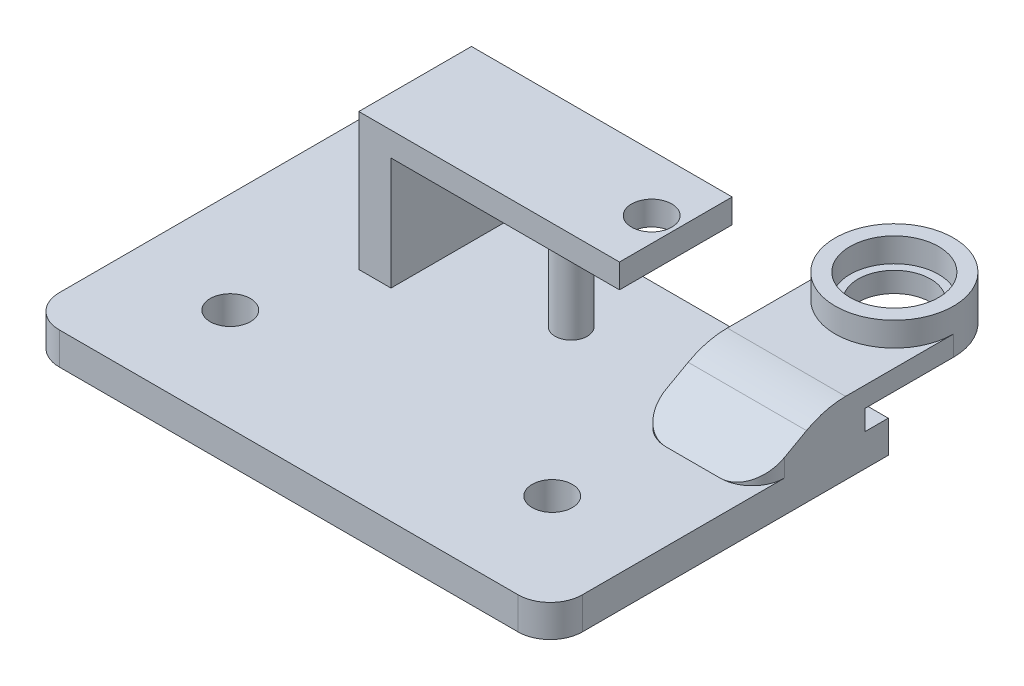
SolidWorks part; units mm, degrees
ref_plane "Front Plane" through (0, 0, 0) normal (0, 0, 1) x (1, 0, 0)
ref_plane "Top Plane" through (0, 0, 0) normal (0, 1, 0) x (1, 0, 0)
ref_plane "Right Plane" through (0, 0, 0) normal (1, 0, 0) x (0, 0, -1)
sketch "Sketch1" plane through (0, 0, 0) normal (0, 1, 0) x (1, 0, 0)
  line L1 (4, 0) -> (61, 0)
  line L2 (0, 4) -> (0, 42)
  line L3 (0, 42) -> (65, 42)
  line L4 (65, 4) -> (65, 42)
  arc A0 (65, 4) -> (61, 0) centre (61, 4) cw
  arc A1 (0, 4) -> (4, 0) centre (4, 4) ccw
  circle A2 centre (12.5, 12.75) radius 2.5
  circle A3 centre (52.5, 12.75) radius 2.5
  point P7 (65, 0)
  point P10 (0, 0)
  dimension "D3" = 4
  dimension "D8" = 5
  dimension "D9" = 5
  dimension "D1" = 42
  dimension "D2" = 65
  dimension "D4" = 12.75
  dimension "D5" = 40
  dimension "D6" = 12.75
  dimension "D7" = 12.5
extrude "Boss-Extrude1" add sketch "Sketch1" along normal blind 4
sketch "Sketch2" plane through (0, 4, 0) normal (0, 1, 0) x (1, 0, 0)
  line L0 (0, 42) -> (0, 4) construction
  line L1 (65, 42) -> (0, 42)
  line L2 (65, 42) -> (65, 38)
  line L3 (65, 38) -> (0, 38)
  line L4 (0, 42) -> (0, 38)
  circle A0 centre (61, 4) radius 2
  circle A1 centre (4, 4) radius 2
  dimension "D1" = 4
  dimension "D2" = 4
  dimension "D3" = 4
extrude "Boss-Extrude2" add sketch "Sketch2" along normal blind 13
sketch "Sketch3" plane through (0, 17, 0) normal (0, 1, 0) x (1, 0, 0)
  line L0 (4, 0) -> (61, 0) construction
  line L1 (0, 42) -> (65, 42)
  line L2 (0, 42) -> (0, 4)
  line L3 (4, 0) -> (61, 0)
  line L4 (65, 42) -> (65, 4)
  arc A0 (0, 4) -> (4, 0) centre (4, 4) ccw
  arc A1 (61, 0) -> (65, 4) centre (61, 4) ccw
  dimension "D1" = 4
  dimension "D2" = 0
  dimension "D3" = 65
extrude "Boss-Extrude3" add sketch "Sketch3" along normal blind 4
sketch "Sketch4" plane through (0, 0, -42) normal (0, 0, -1) x (-1, 0, 0)
  line L0 (-65, 21) -> (-65, 0) construction
  line L1 (-65, 17) -> (0, 17)
  line L2 (-65, 17) -> (-65, 21)
  line L3 (-65, 21) -> (0, 21)
  line L4 (0, 17) -> (0, 21)
  dimension "D1" = 4
extrude "Boss-Extrude4" add sketch "Sketch4" along normal blind 20
fillet "Fillet1" radius 4 2 edges at (65, 19, -62) (0, 19, -62)
sketch "Sketch6" plane through (0, 21, 0) normal (0, 1, 0) x (1, 0, 0)
  line L0 (65, 50.1043) -> (57.65, 50.1043)
  line L1 (4, 62) -> (61, 62) construction
  line L2 (57.65, 0) -> (57.65, 62)
  line L3 (65, 4) -> (65, 58) construction
  line L6 (45.5, 32.1043) -> (65, 32.1043)
  line L8 (45.5, 0) -> (45.5, 62)
  circle A0 centre (57.65, 50.1043) radius 2.5
  circle A1 centre (45.5, 32.1043) radius 2.5
  dimension "D2" = 5
  dimension "D3" = 0
  dimension "D4" = 5
  dimension "D1" = 62
  dimension "D5" = 62
  dimension "D6" = 29.8957
  dimension "D7" = 11.8957
  dimension "D8" = 0
  dimension "D9" = 0
  dimension "D10" = 7.35
  dimension "D11" = 12.15
  dimension "D12" = 7.35
  dimension "D13" = 11.8957
  dimension "D14" = 29.8957
extrude "Cut-Extrude1" cut sketch "Sketch6" against normal blind 20 contours L8 A1 | L8 A1 L6 | L6 A1 L8 | L2 A0 L0 | A0 region at (58.711, 21, -49.0433) region at (46.561, 21, -31.0433) region at (46.561, 21, -33.1654) region at (44.439, 21, -32.1043)
sketch "Sketch7" plane through (0, 0, 0) normal (0, 0, 1) x (1, 0, 0)
  line L0 (4, 21) -> (61, 21) construction
  line L1 (50, 21) -> (0, 21)
  line L2 (50, 21) -> (50, 0)
  line L3 (50, 0) -> (0, 0)
  line L4 (0, 21) -> (0, 0)
  line L5 (50, 4) -> (0, 4)
  line L6 (4, 4) -> (61, 4) construction
  line M5 (4, 17) -> (61, 17)
  line M7 (61, 21) -> (4, 21)
  line M8 (4, 21) -> (4, 17)
  dimension "D1" = 50
extrude "Cut-Extrude2" cut sketch "Sketch7" against normal blind 80 contours L5 L2 L1 L4 M5 M8 | L2 M7 M8 M5 region at (27, 19, 0) region at (24.4474, 10.7042, 0)
ref_plane "Plane1" through (57.5, 0, 0) normal (1, 0, 0) x (0, 0, -1)
sketch "Sketch10" plane through (57.5, 0, 0) normal (1, 0, 0) x (0, 0, -1)
  line L0 (33, 4) -> (38, 9)
  line L1 (4, 4) -> (38, 4) construction
  line L2 (38, 17) -> (38, 4) construction
  line L3 (38, 9) -> (38, 4)
  line L4 (38, 4) -> (33, 4)
  dimension "D1" = 5
  dimension "D2" = 5
extrude "Boss-Extrude6" add sketch "Sketch10" along normal blind 2.5 and the other way blind 2.5
sketch "Sketch11" plane through (0, 21, 0) normal (0, 1, 0) x (1, 0, 0)
  line L0 (57.5, 0) -> (57.5, 42)
  line L1 (50, 0) -> (61, 0) construction
  line L2 (57.5, -11.55) -> (57.5, 11.55) construction
  line L4 (50, 62) -> (50, 0) construction
  line L6 (50, 44) -> (50, 0)
  line L7 (50, 0) -> (57.5, 0)
  line L8 (55.5, 44) -> (50, 44)
  arc A2 (57.5, 42) -> (55.5, 44) centre (55.5, 42) ccw
  point P12 (57.5, 31)
  point P13 (57.5, 44)
  point P15 (50, 31)
  line M10 (50, 62) -> (50, 0)
  line M11 (50, 0) -> (61, 0)
  dimension "D1" = 44
  dimension "D3" = 2
  dimension "D2" = 7.5
extrude "Cut-Extrude3" cut sketch "Sketch11" against normal up to surface (17 mm away) contours L0 M10 M11 region at (53.7414, 21, -21.9438) up to face at (52.5, 4, -10.25)
fillet "Fillet2" radius 4 1 edges at (57.5, 19, 0)
sketch "Sketch8" plane through (0, 4, 0) normal (0, 1, 0) x (1, 0, 0)
  circle A0 centre (45.5, 32.1043) radius 6
  circle A1 centre (45.5, 32.1043) radius 2.5
  dimension "D1" = 5
  dimension "D2" = 12
extrude "Boss-Extrude5" add sketch "Sketch8" along normal blind 5
fillet "Fillet3" radius 4 1 edges at (50, 19, -62)
sketch "Sketch12" plane through (57.5, 0, 0) normal (1, 0, 0) x (0, 0, -1)
  line L0 (42, 12) -> (47, 17)
  line L1 (42, 17) -> (42, 0) construction
  line L2 (58, 17) -> (42, 17) construction
  line L3 (47, 17) -> (42, 17)
  line L4 (42, 17) -> (42, 12)
  dimension "D1" = 5
  dimension "D2" = 5
extrude "Boss-Extrude7" add sketch "Sketch12" along normal up to surface (7.5 mm away) from offset 4 up to face at (65, 11.8, -29.2)
sketch "Sketch13" plane through (0, 0, 0) normal (0, -1, 0) x (1, 0, 0)
  circle A0 centre (45.5, -32.1043) radius 4.5
  dimension "D1" = 9
extrude "Cut-Extrude4" cut sketch "Sketch13" against normal blind 6
sketch "Sketch14" plane through (0, 21, 0) normal (0, 1, 0) x (1, 0, 0)
  line L0 (54.2644, 44) -> (54.2644, 62)
  line L1 (55.5, 44) -> (50, 44) construction
  line L2 (54, 62) -> (61, 62) construction
  line L3 (54.2644, 62) -> (40.9821, 62)
  line L4 (40.9821, 62) -> (40.9821, 44)
  line L5 (40.9821, 44) -> (54.2644, 44)
  line L6 (50, 58) -> (50, 44) construction
  dimension "D1" = 13.2823
  dimension "D2" = 4.2644
extrude "Cut-Extrude5" cut sketch "Sketch14" against normal blind 6 contours L5 L0 L3 L4
fillet "Fillet5" radius 4 2 edges at (54.2644, 19, -62) (54.2644, 19, -44)
sketch "Sketch15" plane through (0, 0, -42) normal (0, 0, -1) x (-1, 0, 0)
  line L1 (-65, 0) -> (0, 0)
  line L2 (-65, 0) -> (-65, 4)
  line L3 (-65, 4) -> (0, 4)
  line L4 (0, 0) -> (0, 4)
extrude "Boss-Extrude8" add sketch "Sketch15" along normal blind 20
sketch "Sketch16" plane through (0, 21, 0) normal (0, 1, 0) x (1, 0, 0)
  circle A0 centre (57.65, 50.1043) radius 2.5
extrude "Cut-Extrude6" cut sketch "Sketch16" against normal blind 30
sketch "Sketch18" plane through (0, 4, 0) normal (0, 1, 0) x (1, 0, 0)
  line L0 (4, 0) -> (61, 0) construction
  line L1 (30.2417, 0) -> (35.6936, 0)
  line L2 (30.2417, 0) -> (30.2417, 11.016)
  line L3 (30.2417, 11.016) -> (35.6936, 11.016)
  line L4 (35.6936, 0) -> (35.6936, 11.016)
  line L5 (0, 62) -> (0, 4) construction
  dimension "D1" = 11.016
  dimension "D2" = 5.4519
  dimension "D3" = 30.2417
extrude "Boss-Extrude9" add sketch "Sketch18" along normal up to surface (17 mm away) up to face at (59.0045, 21, -38.1085)
sketch "Sketch19" plane through (57.5, 0, 0) normal (1, 0, 0) x (0, 0, -1)
  line L1 (0, 4) -> (62, 4)
  line L2 (0, 4) -> (0, 21)
  line L3 (0, 21) -> (62, 21)
  line L4 (62, 4) -> (62, 21)
extrude "Cut-Extrude7" cut sketch "Sketch19" along normal up to surface (7.5 mm away) and the other way up to surface (3.2356 mm away) up to face at (65, 10.6154, -35.6154) other way up to face at (54.2644, 19, -52.6626)
sketch "Sketch20" plane through (0, 4, 0) normal (0, 1, 0) x (1, 0, 0)
  circle A0 centre (57.65, 50.1043) radius 4
  circle A1 centre (57.65, 50.1043) radius 2.5
  dimension "D1" = 5
  dimension "D2" = 8
extrude "Boss-Extrude10" add sketch "Sketch20" along normal up to surface (5 mm away) up to face at (45.5, 9, -26.1043)
sketch "Sketch21" plane through (0, 4, 0) normal (0, 1, 0) x (1, 0, 0)
  line L0 (0, 62) -> (0, 4) construction
  line L1 (16.1112, 25.1043) -> (20.1112, 25.1043)
  line L2 (16.1112, 25.1043) -> (16.1112, 39.1043)
  line L3 (16.1112, 39.1043) -> (20.1112, 39.1043)
  line L4 (20.1112, 25.1043) -> (20.1112, 39.1043)
  circle A0 centre (45.5, 32.1043) radius 6 construction
  circle A1 centre (45.5, 32.1043) radius 6 construction
  dimension "D1" = 7
  dimension "D2" = 7
  dimension "D3" = 4
  dimension "D4" = 16.1112
extrude "Boss-Extrude11" add sketch "Sketch21" along normal up to surface (17 mm away) up to face at (32.9676, 21, -5.508)
sketch "Sketch22" plane through (20.1112, 0, 0) normal (1, 0, 0) x (0, 0, -1)
  line L0 (39.1043, 21) -> (39.1043, 4) construction
  line L1 (25.1043, 21) -> (39.1043, 21)
  line L2 (25.1043, 21) -> (25.1043, 18)
  line L3 (25.1043, 18) -> (39.1043, 18)
  line L4 (39.1043, 21) -> (39.1043, 18)
  dimension "D1" = 3
extrude "Boss-Extrude12" add sketch "Sketch22" along normal up to surface (37.3888 mm away) up to plane "Plane1"
sketch "Sketch24" plane through (0, 9, 0) normal (0, 1, 0) x (1, 0, 0)
  circle A0 centre (45.5, 32.1043) radius 2.5
  dimension "D1" = 5
extrude "Cut-Extrude8" cut sketch "Sketch24" along normal up to surface (12 mm away) up to face at (36.8056, 21, -32.1043)
sketch "Sketch25" plane through (35.6936, 0, 0) normal (1, 0, 0) x (0, 0, -1)
  line L1 (0, 4) -> (11.016, 4)
  line L2 (0, 4) -> (0, 21)
  line L3 (0, 21) -> (11.016, 21)
  line L4 (11.016, 4) -> (11.016, 21)
extrude "Cut-Extrude9" cut sketch "Sketch25" against normal up to surface (5.4519 mm away) up to face at (30.2417, 12.5, -5.508)
sketch "Sketch26" plane through (0, 9, 0) normal (0, 1, 0) x (1, 0, 0)
  circle A0 centre (45.5, 32.1043) radius 6
extrude "Cut-Extrude10" cut sketch "Sketch26" against normal up to surface (5 mm away) up to face at (32.5, 4, -21.7239)
sketch "Sketch27" plane through (0, 4, 0) normal (0, 1, 0) x (1, 0, 0)
  circle A0 centre (45.5, 32.1043) radius 4.5
extrude "Boss-Extrude13" add sketch "Sketch27" against normal up to surface (4 mm away) up to face at (57.65, 0, -47.6043)
sketch "Sketch29" plane through (0, 4, 0) normal (0, 1, 0) x (1, 0, 0)
  line L0 (65, 4) -> (65, 62) construction
  line L1 (61, 25.1043) -> (54.3, 25.1043)
  line L2 (65, 29.1043) -> (65, 39.1043)
  line L3 (65, 39.1043) -> (50.3, 39.1043)
  line L4 (50.3, 29.1043) -> (50.3, 39.1043)
  line L5 (57.5, 39.1043) -> (16.1112, 39.1043) construction
  arc A0 (61, 25.1043) -> (65, 29.1043) centre (61, 29.1043) ccw
  arc A1 (54.3, 25.1043) -> (50.3, 29.1043) centre (54.3, 29.1043) cw
  point P10 (65, 25.1043)
  dimension "D3" = 4
  dimension "D1" = 14.7
  dimension "D2" = 14
extrude "Boss-Extrude14" add sketch "Sketch29" along normal up to surface (5 mm away) up to face at (57.65, 9, -47.6043)
sketch "Sketch30" plane through (0, 0, -39.1043) normal (0, 0, -1) x (-1, 0, 0)
  line L0 (-65, 6.5) -> (-50.3, 6.5)
  line L1 (-65, 9) -> (-65, 4) construction
  line L2 (-50.3, 9) -> (-50.3, 4) construction
  line L3 (-50.3, 6.5) -> (-50.3, 9)
  line L4 (-50.3, 9) -> (-65, 9)
  line L5 (-65, 9) -> (-65, 6.5)
sketch "Sketch31" plane through (65, 0, 0) normal (1, 0, 0) x (0, 0, -1)
  line L0 (25.1043, 4) -> (34.1043, 9)
  line L1 (29.1043, 9) -> (39.1043, 9) construction
  line L2 (34.1043, 9) -> (34.1043, 4)
  line L3 (34.1043, 4) -> (25.1043, 4)
  line L4 (34.1043, 9) -> (25.1043, 9)
  line L5 (25.1043, 9) -> (25.1043, 4)
  line L6 (25.1043, 4) -> (34.1043, 9)
  line M8 (39.1043, 9) -> (29.1043, 9)
  line M9 (29.1043, 9) -> (29.1043, 4)
extrude "Cut-Extrude11" cut sketch "Sketch31" along direction (1, 0, 0) on the side against the normal up to surface (14.7 mm away) contours L4 L5 L0 M9 | L0 M9 M8 region at (65, 7.0026, -26.9139) region at (65, 8.0741, -30.771) up to face at (50.3, 6.5, -34.1043)
fillet "Fillet6" radius 10 1 edges at (57.65, 9, -34.1043)
sketch "Sketch32" plane through (0, 9, 0) normal (0, 1, 0) x (1, 0, 0)
  line L0 (50.3, 50.1043) -> (50.3, 39.1043)
  line L1 (50.3, 39.1043) -> (65, 39.1043) construction
  line L2 (50.3, 39.1043) -> (65, 39.1043)
  line L3 (65, 39.1043) -> (65, 50.1043)
  line L4 (65, 50.1043) -> (50.3, 50.1043)
  circle A0 centre (57.65, 50.1043) radius 7.35
  circle A1 centre (57.65, 50.1043) radius 2.5
  circle M2 centre (57.65, 50.1043) radius 2.5
  circle M3 centre (57.65, 50.1043) radius 4
  dimension "D1" = 14.7
  dimension "D2" = 5
extrude "Boss-Extrude15" add sketch "Sketch32" against normal up to vertex (2.5 mm away) contours A0 L0 L2 L3 | L4 A0 M3 | L4 A0 M3 | L4 M3 M2 | L4 M3 M2 region at (57.65, 9, -41.9754) region at (57.65, 9, -57.29) region at (51.975, 9, -49.94) region at (57.65, 9, -54.0149) region at (54.4, 9, -50.0149) up to point (50.3, 6.5, -39.1043)
sketch "Sketch28" plane through (65, 0, 0) normal (1, 0, 0) x (0, 0, -1)
  line L0 (4, 4) -> (29.1043, 4) construction
  line L1 (62, 0) -> (42, 0)
  line L2 (62, 0) -> (62, 4)
  line L3 (62, 4) -> (42, 4)
  line L4 (42, 0) -> (42, 4)
  line L5 (42, 4) -> (42, 6.5)
  line L6 (39.1043, 6.5) -> (50.1043, 6.5) construction
  line L7 (42, 6.5) -> (62, 6.5)
  line L8 (62, 6.5) -> (62, 4)
  line L9 (42, 4) -> (62, 4)
  line M2 (62, 0) -> (62, 4)
  line M3 (62, 4) -> (39.1043, 4)
  line M5 (4, 0) -> (62, 0)
  line M16 (39.1043, 6.5) -> (50.1043, 6.5)
  dimension "D1" = 20
extrude "Cut-Extrude12" cut sketch "Sketch28" against normal up to surface (65 mm away) contours L8 L7 L5 M16 M3 | L4 M5 M2 M3 region at (65, 2, -52) region at (65, 5.25, -52) up to face at (0, 2, -33)
sketch "Sketch33" plane through (0, 21, 0) normal (0, 1, 0) x (1, 0, 0)
  line L0 (16.1112, 25.1043) -> (57.5, 25.1043) construction
  line L1 (48.5, 25.1043) -> (57.5, 25.1043)
  line L2 (48.5, 25.1043) -> (48.5, 39.1043)
  line L3 (48.5, 39.1043) -> (57.5, 39.1043)
  line L4 (57.5, 25.1043) -> (57.5, 39.1043)
  line L5 (65, 39.1043) -> (50.3, 39.1043) construction
  line L6 (57.5, -11.55) -> (57.5, 11.55) construction
  circle A0 centre (45.5, 32.1043) radius 2.5 construction
  dimension "D1" = 3
extrude "Cut-Extrude13" cut sketch "Sketch33" against normal up to surface (3 mm away) up to face at (45.5, 18, -29.6043)
sketch "Sketch34" plane through (0, 0, -25.1043) normal (0, 0, 1) x (1, 0, 0)
  line L0 (20.1112, 14) -> (24.1112, 18)
  line L1 (20.1112, 18) -> (20.1112, 4) construction
  line L2 (48.5, 18) -> (20.1112, 18) construction
  line L3 (24.1112, 18) -> (20.1112, 18)
  line L4 (20.1112, 18) -> (20.1112, 14)
  dimension "D1" = 4
  dimension "D2" = 4
extrude "Boss-Extrude18" add sketch "Sketch34" along normal blind 3 from offset 8.5 offset against normal yes
sketch "Sketch35" plane through (0, 21, 0) normal (0, 1, 0) x (1, 0, 0)
  line L0 (48.5, 39.1043) -> (16.1112, 39.1043) construction
  circle A0 centre (35.5, 32.1043) radius 2
  circle A1 centre (45.5, 32.1043) radius 2.5 construction
  dimension "D1" = 4
  dimension "D2" = 7
  dimension "D3" = 10
extrude "Boss-Extrude19" add sketch "Sketch35" against normal up to surface (17 mm away) up to face at (18.1112, 4, -32.1043)
sketch "Sketch36" plane through (0, 6.5, 0) normal (0, -1, 0) x (1, 0, 0)
  circle A0 centre (57.65, -50.1043) radius 4.5
  dimension "D1" = 9
sketch "Sketch37" plane through (0, 9, 0) normal (0, 1, 0) x (1, 0, 0)
  circle A0 centre (57.65, 50.1043) radius 5.5
  circle A1 centre (57.65, 50.1043) radius 7.35
  dimension "D1" = 11
  dimension "D2" = 14.7
extrude "Boss-Extrude20" add sketch "Sketch37" along normal blind 3
sketch "Sketch38" plane through (0, 6.5, 0) normal (0, -1, 0) x (1, 0, 0)
  circle A0 centre (57.65, -50.1043) radius 4.5
  dimension "D1" = 9
extrude "Cut-Extrude14" cut sketch "Sketch38" against normal blind 3
ref_plane "Plane2" through (-10, 0, 0) normal (-1, 0, 0) x (0, 0, 1)
